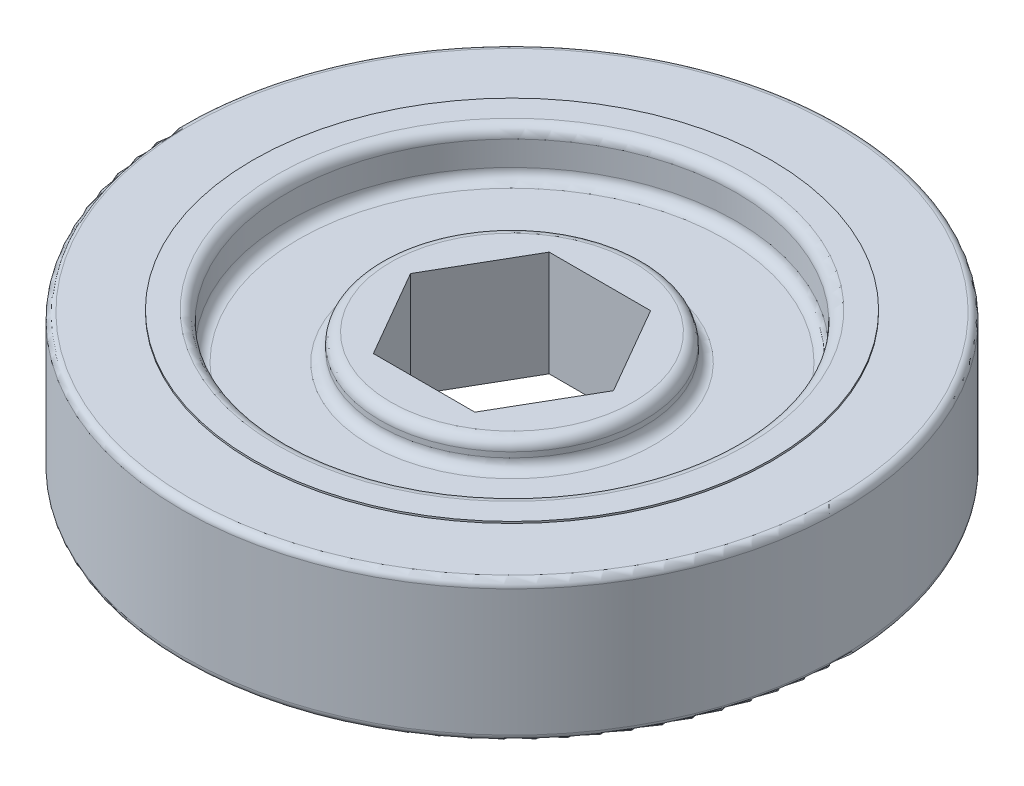
SolidWorks part; units mm, degrees
ref_plane "Front Plane" through (0, 0, 0) normal (0, 0, 1) x (1, 0, 0)
ref_plane "Top Plane" through (0, 0, 0) normal (0, 1, 0) x (1, 0, 0)
ref_plane "Right Plane" through (0, 0, 0) normal (1, 0, 0) x (0, 0, -1)
sketch "Sketch1" plane through (0, 0, 0) normal (0, 1, 0) x (1, 0, 0)
  line L1 (3.6662, 6.35) -> (-3.6662, 6.35)
  line L2 (-3.6662, 6.35) -> (-7.3323, 0)
  line L3 (-7.3323, 0) -> (-3.6662, -6.35)
  line L4 (-3.6662, -6.35) -> (3.6662, -6.35)
  line L5 (3.6662, -6.35) -> (7.3323, 0)
  line L6 (7.3323, 0) -> (3.6662, 6.35)
  circle A0 centre (0, 0) radius 23.8125
  circle A1 centre (0, 0) radius 6.35 construction
  circle A2 centre (0, 0) radius 18.7325
  circle A3 centre (0, 0) radius 16.1925
  circle A4 centre (0, 0) radius 9.525
  dimension "D1" = 47.625
  dimension "D3" = 5.08
  dimension "D4" = 2.54
  dimension "D5" = 19.05
  dimension "D2" = 12.7
extrude "Boss-Extrude1" add sketch "Sketch1" along normal mid plane 10.16 contours A0 A2 region at (-23.139, 0, 0)
extrude "Boss-Extrude2" add sketch "Sketch1<3>" along normal mid plane 10.414 contours A2 A3 region at (-18.2027, 0, 0)
sketch "Sketch1<3>" plane through (0, 0, 0) normal (0, 1, 0) x (1, 0, 0) same geometry as "Sketch1"
extrude "Boss-Extrude3" add sketch "Sketch1<4>" along normal mid plane 7.62 separate body contours A4 L6 L5 L4 L3 L2 L1 region at (-9.2556, 0, 0)
sketch "Sketch1<4>" plane through (0, 0, 0) normal (0, 1, 0) x (1, 0, 0) same geometry as "Sketch1"
extrude "Boss-Extrude4" add sketch "Sketch1<5>" along normal mid plane 3.81 contours A3 A4 region at (-15.7345, 0, 0)
sketch "Sketch1<5>" plane through (0, 0, 0) normal (0, 1, 0) x (1, 0, 0) same geometry as "Sketch1"
fillet "Fillet1" radius 0.762 8 edges at (0, -1.905, 16.1925) (0, 5.207, 16.1925) (0, 1.905, 16.1925) (0, 3.81, 9.525) (0, 1.905, 9.525) (0, -5.207, 16.1925) (0, -3.81, 9.525) (0, -1.905, 9.525)
fillet "Fillet2" radius 0.508 2 edges at (0, -5.08, 23.8125) (0, 5.08, 23.8125)
